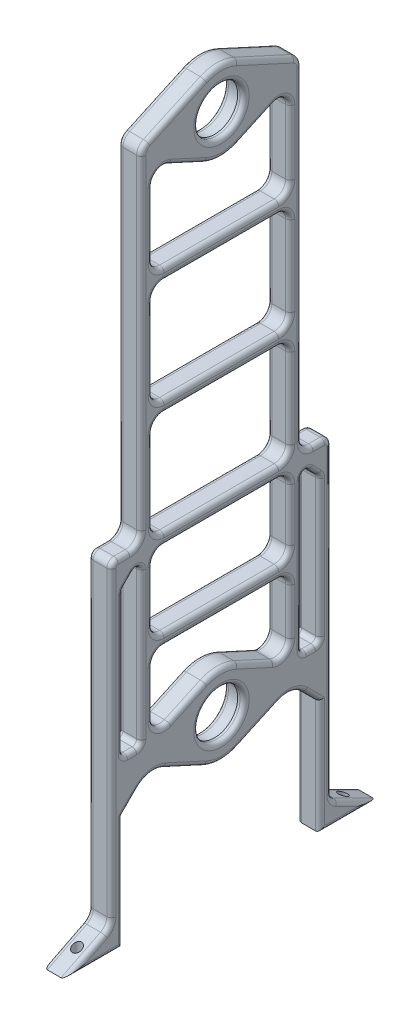
SolidWorks part; units mm, degrees
ref_plane "Front Plane" through (0, 0, 0) normal (0, 0, 1) x (1, 0, 0)
ref_plane "Top Plane" through (0, 0, 0) normal (0, 1, 0) x (1, 0, 0)
ref_plane "Right Plane" through (0, 0, 0) normal (1, 0, 0) x (0, 0, -1)
sketch "Croquis1" plane through (0, 0, 0) normal (1, 0, 0) x (0, 0, -1)
  line L0 (3.1865, 95.253) -> (51.7799, 95.253) construction
  line L1 (15, 74) -> (5, 64)
  line L2 (0, 0) -> (5, 0)
  line L3 (0, 0) -> (0, 155)
  line L4 (0, 155) -> (5, 155)
  line L5 (5, 0) -> (5, 155)
  line L6 (5, 155) -> (91, 155)
  line L7 (5, 155) -> (5, 150)
  line L8 (5, 150) -> (91, 150)
  line L9 (91, 155) -> (91, 150)
  line L10 (91, 155) -> (96, 155)
  line L11 (91, 155) -> (91, 0)
  line L12 (91, 0) -> (96, 0)
  line L13 (96, 155) -> (96, 0)
  line L14 (13, 305) -> (18, 305)
  line L15 (13, 305) -> (13, 79)
  line L16 (13, 79) -> (18, 79)
  line L17 (18, 305) -> (18, 79)
  line L18 (5, 79) -> (91, 79)
  line L19 (5, 79) -> (5, 74)
  line L20 (5, 74) -> (91, 74)
  line L21 (91, 79) -> (91, 74)
  line L22 (83, 79) -> (78, 79)
  line L23 (83, 79) -> (83, 305)
  line L24 (83, 305) -> (78, 305)
  line L25 (78, 79) -> (78, 305)
  line L26 (18, 305) -> (78, 305)
  line L27 (18, 305) -> (18, 300)
  line L28 (18, 300) -> (78, 300)
  line L29 (78, 305) -> (78, 300)
  line L30 (18, 205) -> (78, 205)
  line L31 (18, 205) -> (18, 200)
  line L32 (18, 200) -> (78, 200)
  line L33 (78, 205) -> (78, 200)
  line L34 (18, 255) -> (78, 255)
  line L35 (18, 255) -> (18, 250)
  line L36 (18, 250) -> (78, 250)
  line L37 (78, 255) -> (78, 250)
  line L38 (18, 117) -> (78, 117)
  line L39 (18, 117) -> (18, 112)
  line L40 (18, 112) -> (78, 112)
  line L41 (78, 117) -> (78, 112)
  line L42 (81, 74) -> (91, 64)
  line L43 (78, 52.6217) -> (83, 52.6217) construction
  line L44 (48, 117) -> (48, 112) construction
  line L45 (48, 155) -> (48, 150) construction
  line L46 (48, 200) -> (48, 205) construction
  line L47 (48, 255) -> (48, 250) construction
  line L48 (48, 250) -> (48, 255) construction
  line L49 (48, 305) -> (48, 300) construction
  line L50 (22.0711, 74) -> (5, 56.9289)
  line L51 (73.9289, 74) -> (91, 56.9289)
  line L52 (48, 300) -> (48, 255) construction
  line L53 (48, 250) -> (48, 205) construction
  line L54 (48, 205) -> (48, 334.4288) construction
  line L55 (48, 200) -> (48, 155) construction
  line L56 (48, 150) -> (48, 117) construction
  line L57 (48, 112) -> (48, 79) construction
  line L58 (48, 74) -> (48, 0) construction
  line L59 (13, 150) -> (5, 142)
  line L60 (83, 150) -> (91, 142)
  point P59 (48, 79)
  point P64 (48, 74)
  dimension "D2" = 70
  dimension "D3" = 5
  dimension "D4" = 45
  dimension "D5" = 45
  dimension "D6" = 5
  dimension "D7" = 5
  dimension "D8" = 5
  dimension "D9" = 10
  dimension "D10" = 10
  dimension "D11" = 45
  dimension "D12" = 45
  dimension "D13" = 8
  dimension "D14" = 74
  dimension "D16" = 150
extrude "Saliente-Extruir1" add sketch "Croquis1" along normal blind 10 contours L2 L5 L4 L3 | L50 L20 L1 L5 | L5 L20 L11 L18 L16 | L13 L10 L9 L11 L12 | L20 L51 L11 L42 | L25 L18 L23 L8 | L17 L8 L15 L16 | L17 L40 L25 L38 | L15 L6 L5 L8 | L17 L6 L15 L8 | L8 L25 L6 L17 | L17 L14 L15 L6 | L25 L8 L23 L6 | L25 L6 L23 L24 | L23 L8 L9 L6 | L17 L28 L25 L26 | L17 L36 L25 L34 | L17 L32 L25 L30 | L59 L8 L5 | L8 L60 L11 | L20 L5 L1 | L20 L42 L11 region at (0, 67.0783, -11.9217) region at (0, 70.6667, -8.3333) region at (0, 76.5, -48) region at (0, 77.5, -2.5) region at (0, 67.0783, -84.0783) region at (0, 147.3333, -7.6667) region at (0, 114.5, -15.5) region at (0, 70.6667, -87.6667) region at (0, 77.5, -93.5) region at (0, 152.5, -9) region at (0, 152.5, -15.5) region at (0, 152.5, -48) region at (0, 230, -15.5) region at (0, 114.5, -48) region at (0, 114.5, -80.5) region at (0, 152.5, -80.5) region at (0, 147.3333, -88.3333) region at (0, 152.5, -87) region at (0, 230, -80.5) region at (0, 202.5, -48) region at (0, 302.5, -48) region at (0, 252.5, -48)
sketch "Croquis2" plane through (10, 0, 0) normal (1, 0, 0) x (0, 0, -1)
  line L0 (48, 301.5) -> (34.0198, 331.4807) construction
  line L1 (48, 301.5) -> (81.08, 301.5) construction
  line L2 (48, 73.5) -> (48, 301.5) construction
  line L3 (106.66, 301.5) -> (55.5, 301.5)
  line L4 (22.42, 73.5) -> (22.42, 301.5)
  line L5 (73.58, 301.5) -> (73.58, 136.78) construction
  line L6 (106.66, 301.5) -> (106.66, 272.7)
  line L7 (106.66, 272.7) -> (55.5, 272.7)
  line L8 (55.5, 301.5) -> (55.5, 272.7)
  line L9 (22.42, 301.5) -> (22.42, 73.5) construction
  line L10 (8.4398, 331.4807) -> (59.5998, 331.4807)
  line L11 (8.4398, 331.4807) -> (8.4398, 302.6807)
  line L12 (8.4398, 302.6807) -> (59.5998, 302.6807)
  line L13 (59.5998, 331.4807) -> (59.5998, 302.6807)
  line L18 (73.58, 136.78) -> (73.58, 73.5) construction
  line L19 (48, 73.5) -> (14.92, 73.5) construction
  line L20 (-10.66, 73.5) -> (40.5, 73.5)
  line L21 (-10.66, 73.5) -> (-10.66, 44.7)
  line L22 (-10.66, 44.7) -> (40.5, 44.7)
  line L23 (40.5, 73.5) -> (40.5, 44.7)
  line L24 (36.4002, 43.5193) -> (87.5602, 43.5193)
  line L25 (36.4002, 43.5193) -> (36.4002, 14.7193)
  line L26 (36.4002, 14.7193) -> (87.5602, 14.7193)
  line L27 (87.5602, 43.5193) -> (87.5602, 14.7193)
  line L28 (48, 73.5) -> (61.9802, 43.5193) construction
  line L29 (62.5413, 301.5) -> (55.5, 295.71)
  line L30 (55.5, 295.71) -> (59.5573, 272.7)
  line L32 (52.5584, 331.4807) -> (59.5998, 325.6907)
  line L33 (59.5998, 325.6907) -> (55.5425, 302.6807)
  line L34 (73.58, 73.5) -> (73.58, 301.5)
  line L35 (-10.66, 124.84) -> (40.5, 124.84)
  line L36 (-10.66, 124.84) -> (-10.66, 96.04)
  line L37 (-10.66, 96.04) -> (40.5, 96.04)
  line L38 (40.5, 124.84) -> (40.5, 96.04)
  line L39 (55.5, 96.14) -> (106.66, 96.14)
  line L40 (55.5, 96.14) -> (55.5, 67.34)
  line L41 (55.5, 67.34) -> (106.66, 67.34)
  line L42 (106.66, 96.14) -> (106.66, 67.34)
  line L43 (-10.66, 176.18) -> (40.5, 176.18)
  line L44 (-10.66, 176.18) -> (-10.66, 147.38)
  line L45 (-10.66, 147.38) -> (40.5, 147.38)
  line L46 (40.5, 176.18) -> (40.5, 147.38)
  line L47 (-10.66, 227.52) -> (40.5, 227.52)
  line L48 (-10.66, 227.52) -> (-10.66, 198.72)
  line L49 (-10.66, 198.72) -> (40.5, 198.72)
  line L50 (40.5, 227.52) -> (40.5, 198.72)
  line L51 (-10.66, 278.86) -> (40.5, 278.86)
  line L52 (-10.66, 278.86) -> (-10.66, 250.06)
  line L53 (-10.66, 250.06) -> (40.5, 250.06)
  line L54 (40.5, 278.86) -> (40.5, 250.06)
  line L55 (55.5, 250.16) -> (106.66, 250.16)
  line L56 (55.5, 250.16) -> (55.5, 221.36)
  line L57 (55.5, 221.36) -> (106.66, 221.36)
  line L58 (106.66, 250.16) -> (106.66, 221.36)
  line L59 (55.5, 198.82) -> (106.66, 198.82)
  line L60 (55.5, 198.82) -> (55.5, 170.02)
  line L61 (55.5, 170.02) -> (106.66, 170.02)
  line L62 (106.66, 198.82) -> (106.66, 170.02)
  line L63 (55.5, 147.48) -> (106.66, 147.48)
  line L64 (55.5, 147.48) -> (55.5, 118.68)
  line L65 (55.5, 118.68) -> (106.66, 118.68)
  line L66 (106.66, 147.48) -> (106.66, 118.68)
  line L67 (13, 301.5) -> (83, 301.5) construction
  line L70 (13, 305) -> (13, 155) construction
  line L71 (83, 155) -> (83, 305) construction
  line L73 (18, 300) -> (78, 300) construction
  circle A2 centre (48, 301.5) radius 25.58
  circle A3 centre (48, 73.5) radius 25.58
  arc A4 (22.42, 73.5) -> (73.58, 73.5) centre (48, 73.5) ccw
  arc A5 (73.58, 301.5) -> (22.42, 301.5) centre (48, 301.5) ccw
  point P8 (48, 187.5)
  point P9 (48, 301.5)
  point P11 (81.08, 301.5)
  point P20 (34.0198, 331.4807)
  point P34 (61.9802, 43.5193)
  point P37 (14.92, 73.5)
  point P52 (22.42, 124.84)
  point P53 (73.58, 96.14)
  point P58 (14.92, 124.84)
  point P59 (81.08, 96.14)
  point P80 (22.42, 278.86)
  point P81 (22.42, 227.52)
  point P82 (22.42, 176.18)
  point P83 (73.58, 250.16)
  point P84 (73.58, 198.82)
  point P85 (73.58, 147.48)
  point P86 (14.92, 278.86)
  point P87 (14.92, 227.52)
  point P88 (14.92, 176.18)
  point P93 (81.08, 250.16)
  point P94 (81.08, 198.82)
  point P95 (81.08, 147.48)
  dimension "D1" = 51.16
  dimension "D3" = 51.16
  dimension "D7" = 33.08
  dimension "D30" = 228
  dimension "D4" = 115
  dimension "D5" = 28.8
  dimension "D6" = 115
  dimension "D8" = 140.57
  dimension "D9" = 140.57
  dimension "D10" = 23.01
  dimension "D11" = 23.01
  dimension "D12" = 10
  dimension "D13" = 10
  dimension "D14" = 7.5
  dimension "D15" = 7.5
  dimension "D16" = 51.34
  dimension "D17" = 7.5
  dimension "D18" = 7.5
  dimension "D19" = 7.5
  dimension "D20" = 7.5
  dimension "D21" = 7.5
  dimension "D22" = 7.5
  dimension "D23" = 51.34
  dimension "D24" = 51.34
  dimension "D25" = 51.34
  dimension "D26" = 51.34
  dimension "D27" = 51.34
  dimension "D28" = 51.34
  dimension "D29" = 51.34
  dimension "D31" = 1.5
sketch "Croquis3" plane through (10, 0, 0) normal (1, 0, 0) x (0, 0, -1)
  line L0 (13, 301.5) -> (83, 301.5) construction
  line L1 (106.66, 301.5) -> (55.5, 301.5) construction
  line L2 (13, 305) -> (13, 155) construction
  line L3 (83, 155) -> (83, 305) construction
  line L5 (15.9167, 306.0453) -> (40.7083, 317.4085)
  line L6 (80.0833, 306.0453) -> (55.2917, 317.4085)
  line L7 (15.9167, 296.9547) -> (40.7083, 285.5915)
  line L8 (80.0833, 296.9547) -> (55.2917, 285.5915)
  line L9 (14.4293, 305) -> (13, 305)
  line L10 (13, 305) -> (83, 305) construction
  line L11 (13, 305) -> (13, 301.5)
  line L12 (81.5707, 305) -> (83, 305)
  line L13 (83, 305) -> (83, 301.5)
  circle A0 centre (48, 301.5) radius 10.01
  circle A1 centre (48, 301.5) radius 11.01
  circle A2 centre (48, 301.5) radius 17.5
  circle A3 centre (18, 301.5) radius 5
  circle A4 centre (78, 301.5) radius 5
  line M13 (78, 300) -> (78, 255)
  line M15 (18, 255) -> (18, 300)
  line M16 (18, 300) -> (78, 300)
  line M18 (83, 305) -> (13, 305)
  dimension "D1" = 22.02
  dimension "D2" = 20.02
  dimension "D3" = 35
  dimension "D4" = 10
extrude "Saliente-Extruir2" add sketch "Croquis3" against normal up to surface (10 mm away) contours A2 A1 M18 | A3 A2 L5 M18 | A3 M18 | A3 M18 M15 M16 | A3 M15 M16 | A3 L7 A2 M15 M16 | A2 A1 M16 | A4 A2 L8 M16 M13 | A4 L6 A2 M18 | A3 A2 M16 M18 | A2 A1 M18 M16 | A2 A1 M16 M18 | A4 A2 M18 M16 | A4 M16 M13 | A4 M18 M16 M13 | A4 M18 region at (10, 305.6085, -18) region at (10, 308.8289, -27.6858) region at (10, 318.6296, -48) region at (10, 301.5988, -17.6014) region at (10, 302.574, -26.6181) region at (10, 308.8289, -68.3142) region at (10, 302.5112, -33.8615) region at (10, 305.6085, -78) region at (10, 302.574, -69.3819) region at (10, 302.5112, -62.1385) region at (10, 299.6163, -33.8285) region at (10, 295.0098, -27.5107) region at (10, 298.5471, -19.9168) region at (10, 301.5988, -78.3986) region at (10, 298.5471, -76.0832) region at (10, 295.0098, -68.4893) up to face at (0, 227.5, -48)
sketch "Croquis7" plane through (10, 0, 0) normal (1, 0, 0) x (0, 0, -1)
  line L0 (14.4293, 305) -> (13, 305)
  line L1 (22.0711, 74) -> (73.9289, 74)
  line L7 (81.5707, 305) -> (83, 305)
  line L12 (22.0711, 74) -> (73.9289, 74)
  line L29 (83, 155) -> (83, 305)
  line L30 (83, 155) -> (83, 305)
  line L31 (83, 305) -> (81.5707, 305)
  line L32 (83, 305) -> (81.5707, 305)
  line L33 (80.0833, 306.0453) -> (55.2917, 317.4085)
  line L34 (80.0833, 306.0453) -> (55.2917, 317.4085)
  line L35 (40.7083, 317.4085) -> (15.9167, 306.0453)
  line L36 (40.7083, 317.4085) -> (15.9167, 306.0453)
  line L37 (14.4293, 305) -> (13, 305)
  line L38 (14.4293, 305) -> (13, 305)
  line L39 (13, 305) -> (13, 155)
  line L40 (13, 305) -> (13, 155)
  line L41 (13, 155) -> (0, 155)
  line L42 (13, 155) -> (0, 155)
  line L43 (0, 155) -> (0, 0)
  line L44 (0, 155) -> (0, 0)
  line L45 (0, 0) -> (5, 0)
  line L46 (0, 0) -> (5, 0)
  line L47 (5, 0) -> (5, 56.9289)
  line L48 (5, 0) -> (5, 56.9289)
  line L49 (5, 56.9289) -> (22.0711, 74)
  line L50 (5, 56.9289) -> (22.0711, 74)
  line L51 (73.9289, 74) -> (91, 56.9289)
  line L52 (73.9289, 74) -> (91, 56.9289)
  line L53 (91, 56.9289) -> (91, 0)
  line L54 (91, 56.9289) -> (91, 0)
  line L55 (91, 0) -> (96, 0)
  line L56 (91, 0) -> (96, 0)
  line L57 (96, 0) -> (96, 155)
  line L58 (96, 0) -> (96, 155)
  line L59 (96, 155) -> (83, 155)
  line L60 (96, 155) -> (83, 155)
  circle A0 centre (18, 301.5) radius 5
  arc A1 (15.9167, 306.0453) -> (14.4293, 305) centre (18, 301.5) ccw
  circle A7 centre (78, 301.5) radius 5
  arc A12 (15.9167, 306.0453) -> (14.4293, 305) centre (18, 301.5) ccw
  arc A15 (81.5707, 305) -> (80.0833, 306.0453) centre (78, 301.5) ccw
  arc A16 (81.5707, 305) -> (80.0833, 306.0453) centre (78, 301.5) ccw
  arc A17 (55.2917, 317.4085) -> (40.7083, 317.4085) centre (48, 301.5) ccw
  arc A18 (55.2917, 317.4085) -> (40.7083, 317.4085) centre (48, 301.5) ccw
  dimension "D1" = 0
extrude "Cortar-Extruir5" cut sketch "Croquis7" against normal through all both and the other way through all contours A7 L30 L7 | A0 L0 L40 region at (10, 304.152, -13.4158) region at (10, 304.152, -82.5842)
pattern_linear "MatrizL2" count 2 spacing 228 along (0, -1, 0) of "Saliente-Extruir2"
sketch "Croquis10" plane through (10, 0, 0) normal (1, 0, 0) x (0, 0, -1)
  line L0 (96, 0) -> (96, 155) construction
  line L1 (0, 0) -> (96, 0)
  line L2 (0, 0) -> (0, 7.2193)
  line L3 (0, 7.2193) -> (96, 7.2193)
  line L4 (96, 0) -> (96, 7.2193)
  line L5 (36.4002, 14.7193) -> (87.5602, 14.7193) construction
  dimension "D1" = 7.5
extrude "Cortar-Extruir6" cut sketch "Croquis10" against normal through all both and the other way through all
sketch "Croquis11" plane through (10, 0, 0) normal (1, 0, 0) x (0, 0, -1)
  line L0 (0, 7.2193) -> (-20, 7.2193)
  line L1 (-20, 7.2193) -> (0, 17.2193)
  line L2 (0, 155) -> (0, 0) construction
  line L3 (0, 17.2193) -> (0, 7.2193)
  line L4 (48, 73.5) -> (48, -15.6705) construction
  line L5 (96, 7.2193) -> (116, 7.2193)
  line L6 (96, 17.2193) -> (96, 7.2193)
  line L7 (116, 7.2193) -> (96, 17.2193)
  dimension "D1" = 20
  dimension "D2" = 10
extrude "Saliente-Extruir4" add sketch "Croquis11" against normal up to surface (10 mm away) contours L3 L1 L0 | L5 L7 L6 region at (10, 10.5527, 6.6667) region at (10, 10.5527, -102.6667) up to face at (0, 93.7348, -48)
sketch "Croquis12" plane through (0, 7.2193, 0) normal (0, -1, 0) x (1, 0, 0)
  line L1 (0, -5) -> (0, 20) construction
  circle A0 centre (5, 10) radius 2
  dimension "D1" = 4
  dimension "D2" = 10
  dimension "D3" = 5
extrude "Cortar-Extruir7" cut sketch "Croquis12" against normal through all both and the other way through all
ref_plane "Plano3" through (0, 0, -48) normal (0, 0, 1) x (1, 0, 0)
mirror "Simetría1" about plane through (0, 0, -48) normal (0, 0, 1) of "Cortar-Extruir7"
sketch "Croquis16" plane through (0, 0, 0) normal (-1, 0, 0) x (0, 0, 1)
  circle A0 centre (-48, 301.5) radius 11.01
  circle A1 centre (-48, 73.5) radius 11.01
extrude "Cortar-Extruir8" cut sketch "Croquis16" against normal through all both and the other way through all
sketch "Croquis17" plane through (10, 0, 0) normal (1, 0, 0) x (0, 0, -1)
  circle A0 centre (48, 301.5) radius 11.01
  circle A1 centre (48, 301.5) radius 10.1
  circle A2 centre (48, 73.5) radius 11.01
  circle A3 centre (48, 73.5) radius 10.1
  dimension "D1" = 20.2
  dimension "D2" = 20.2
extrude "Saliente-Extruir5" add sketch "Croquis17" against normal blind 2 contours A0 A1 | A2 A3 region at (10, 301.5, -37.3014) region at (10, 73.5, -37.3014)
sketch "Croquis18" plane through (10, 0, 0) normal (1, 0, 0) x (0, 0, -1)
  line L0 (18, 295.9998) -> (40.7083, 285.5915) construction
  line L1 (18, 295.9998) -> (18, 255) construction
  line L2 (78, 295.9998) -> (55.2917, 285.5915) construction
  line L3 (78, 255) -> (78, 295.9998) construction
  line L4 (18, 112) -> (18, 79.0002) construction
  line L5 (18, 79.0002) -> (40.7083, 89.4085) construction
  line L6 (78, 79.0002) -> (55.2917, 89.4085) construction
  line L7 (78, 79.0002) -> (78, 112) construction
  line L8 (78, 67.9998) -> (55.2917, 57.5915) construction
  line L9 (73.9289, 74) -> (91, 56.9289) construction
  line L10 (5, 56.9289) -> (22.0711, 74) construction
  line L11 (18, 67.9998) -> (40.7083, 57.5915) construction
  line L12 (55.2917, 317.4085) -> (80.0833, 306.0453)
  line L13 (55.2917, 317.4085) -> (80.0833, 306.0453)
  line L14 (83, 301.5) -> (83, 155)
  line L15 (83, 301.5) -> (83, 155)
  line L16 (83, 155) -> (96, 155)
  line L17 (83, 155) -> (96, 155)
  line L18 (96, 155) -> (96, 17.2193)
  line L19 (96, 155) -> (96, 17.2193)
  line L20 (96, 17.2193) -> (116, 7.2193)
  line L21 (96, 17.2193) -> (116, 7.2193)
  line L22 (116, 7.2193) -> (91, 7.2193)
  line L23 (116, 7.2193) -> (91, 7.2193)
  line L24 (91, 7.2193) -> (91, 56.9289)
  line L25 (91, 7.2193) -> (91, 56.9289)
  line L26 (91, 56.9289) -> (79.266, 68.6629)
  line L27 (91, 56.9289) -> (79.266, 68.6629)
  line L28 (78, 68.5) -> (78, 67.9998)
  line L29 (78, 68.5) -> (78, 67.9998)
  line L30 (78, 67.9998) -> (55.2917, 57.5915)
  line L31 (78, 67.9998) -> (55.2917, 57.5915)
  line L32 (91, 7.2193) -> (116, 7.2193)
  line L33 (116, 7.2193) -> (96, 17.2193)
  line L34 (96, 17.2193) -> (96, 155)
  line L35 (96, 155) -> (83, 155)
  line L36 (83, 155) -> (83, 301.5)
  line L37 (80.0833, 306.0453) -> (55.2917, 317.4085)
  line L38 (40.7083, 317.4085) -> (15.9167, 306.0453)
  line L39 (13, 301.5) -> (13, 155)
  line L40 (13, 155) -> (0, 155)
  line L41 (0, 155) -> (0, 17.2193)
  line L42 (0, 17.2193) -> (-20, 7.2193)
  line L43 (-20, 7.2193) -> (5, 7.2193)
  line L44 (5, 7.2193) -> (5, 56.9289)
  line L45 (5, 56.9289) -> (16.734, 68.6629)
  line L46 (18, 68.5) -> (18, 67.9998)
  line L47 (18, 67.9998) -> (40.7083, 57.5915)
  line L48 (55.2917, 57.5915) -> (78, 67.9998)
  line L49 (78, 67.9998) -> (78, 68.5)
  line L50 (79.266, 68.6629) -> (91, 56.9289)
  line L51 (91, 56.9289) -> (91, 7.2193)
  line L52 (91, 7.2193) -> (116, 7.2193)
  line L53 (116, 7.2193) -> (96, 17.2193)
  line L54 (96, 17.2193) -> (96, 155)
  line L55 (96, 155) -> (83, 155)
  line L56 (83, 155) -> (83, 301.5)
  line L57 (80.0833, 306.0453) -> (55.2917, 317.4085)
  line L58 (40.7083, 317.4085) -> (15.9167, 306.0453)
  line L59 (13, 301.5) -> (13, 155)
  line L60 (13, 155) -> (0, 155)
  line L61 (0, 155) -> (0, 17.2193)
  line L62 (0, 17.2193) -> (-20, 7.2193)
  line L63 (-20, 7.2193) -> (5, 7.2193)
  line L64 (5, 7.2193) -> (5, 56.9289)
  line L65 (5, 56.9289) -> (16.734, 68.6629)
  line L66 (18, 68.5) -> (18, 67.9998)
  line L67 (18, 67.9998) -> (40.7083, 57.5915)
  line L68 (55.2917, 57.5915) -> (78, 67.9998)
  line L69 (78, 67.9998) -> (78, 68.5)
  line L70 (79.266, 68.6629) -> (91, 56.9289)
  line L71 (91, 56.9289) -> (91, 7.2193)
  line L72 (40.7083, 57.5915) -> (18, 67.9998)
  line L73 (40.7083, 57.5915) -> (18, 67.9998)
  line L74 (18, 67.9998) -> (18, 68.5)
  line L75 (18, 67.9998) -> (18, 68.5)
  line L76 (16.734, 68.6629) -> (5, 56.9289)
  line L77 (16.734, 68.6629) -> (5, 56.9289)
  line L78 (5, 56.9289) -> (5, 7.2193)
  line L79 (5, 56.9289) -> (5, 7.2193)
  line L80 (5, 7.2193) -> (-20, 7.2193)
  line L81 (5, 7.2193) -> (-20, 7.2193)
  line L82 (-20, 7.2193) -> (0, 17.2193)
  line L83 (-20, 7.2193) -> (0, 17.2193)
  line L84 (0, 17.2193) -> (0, 155)
  line L85 (0, 17.2193) -> (0, 155)
  line L86 (0, 155) -> (13, 155)
  line L87 (0, 155) -> (13, 155)
  line L88 (13, 155) -> (13, 301.5)
  line L89 (13, 155) -> (13, 301.5)
  line L90 (15.9167, 306.0453) -> (40.7083, 317.4085)
  line L91 (15.9167, 306.0453) -> (40.7083, 317.4085)
  line L96 (78, 205) -> (78, 250)
  line L97 (18, 205) -> (78, 205)
  line L98 (18, 250) -> (18, 205)
  line L99 (78, 250) -> (18, 250)
  line L100 (78, 205) -> (78, 250)
  line L101 (18, 205) -> (78, 205)
  line L102 (18, 250) -> (18, 205)
  line L103 (78, 250) -> (18, 250)
  line L104 (78, 155) -> (78, 200)
  line L105 (18, 155) -> (78, 155)
  line L106 (18, 200) -> (18, 155)
  line L107 (78, 200) -> (18, 200)
  line L108 (78, 155) -> (78, 200)
  line L109 (18, 155) -> (78, 155)
  line L110 (18, 200) -> (18, 155)
  line L111 (78, 200) -> (18, 200)
  line L112 (78, 150) -> (18, 150)
  line L113 (78, 117) -> (78, 150)
  line L114 (18, 117) -> (78, 117)
  line L115 (18, 150) -> (18, 117)
  line L116 (78, 150) -> (18, 150)
  line L117 (78, 117) -> (78, 150)
  line L118 (18, 117) -> (78, 117)
  line L119 (18, 150) -> (18, 117)
  line L120 (83, 150) -> (83, 79)
  line L121 (91, 142) -> (83, 150)
  line L122 (91, 79) -> (91, 142)
  line L123 (83, 79) -> (91, 79)
  line L124 (83, 150) -> (83, 79)
  line L125 (91, 142) -> (83, 150)
  line L126 (91, 79) -> (91, 142)
  line L127 (83, 79) -> (91, 79)
  line L128 (13, 150) -> (5, 142)
  line L129 (13, 79) -> (13, 150)
  line L130 (5, 79) -> (13, 79)
  line L131 (5, 142) -> (5, 79)
  line L132 (13, 150) -> (5, 142)
  line L133 (13, 79) -> (13, 150)
  line L134 (5, 79) -> (13, 79)
  line L135 (5, 142) -> (5, 79)
  line L137 (18, 295.9998) -> (18, 255)
  line L138 (40.7083, 285.5915) -> (18, 295.9998)
  line L139 (78, 295.9998) -> (55.2917, 285.5915)
  line L140 (78, 255) -> (78, 295.9998)
  line L141 (18, 255) -> (78, 255)
  line L142 (18, 295.9998) -> (18, 255)
  line L143 (40.7083, 285.5915) -> (18, 295.9998)
  line L144 (78, 295.9998) -> (55.2917, 285.5915)
  line L145 (78, 255) -> (78, 295.9998)
  line L146 (18, 255) -> (78, 255)
  line L147 (78, 79.0002) -> (78, 112)
  line L148 (55.2917, 89.4085) -> (78, 79.0002)
  line L149 (18, 79.0002) -> (40.7083, 89.4085)
  line L150 (18, 112) -> (18, 79.0002)
  line L151 (78, 112) -> (18, 112)
  line L152 (78, 79.0002) -> (78, 112)
  line L153 (55.2917, 89.4085) -> (78, 79.0002)
  line L154 (18, 79.0002) -> (40.7083, 89.4085)
  line L155 (18, 112) -> (18, 79.0002)
  line L156 (78, 112) -> (18, 112)
  circle A0 centre (18.8315, 56.6183) radius 10
  circle A1 centre (77.1685, 56.6183) radius 10
  circle A2 centre (73, 86.7921) radius 5
  circle A3 centre (23, 86.7921) radius 5
  circle A4 centre (23, 288.2079) radius 5
  circle A5 centre (73, 288.2079) radius 5
  arc A6 (83, 301.5) -> (80.0833, 306.0453) centre (78, 301.5) ccw
  arc A7 (83, 301.5) -> (80.0833, 306.0453) centre (78, 301.5) ccw
  arc A8 (78, 68.5) -> (79.266, 68.6629) centre (78, 73.5) ccw
  arc A9 (78, 68.5) -> (79.266, 68.6629) centre (78, 73.5) ccw
  arc A10 (40.7083, 57.5915) -> (55.2917, 57.5915) centre (48, 73.5) ccw
  arc A11 (40.7083, 57.5915) -> (55.2917, 57.5915) centre (48, 73.5) ccw
  arc A12 (83, 301.5) -> (80.0833, 306.0453) centre (78, 301.5) ccw
  arc A13 (55.2917, 317.4085) -> (40.7083, 317.4085) centre (48, 301.5) ccw
  arc A14 (15.9167, 306.0453) -> (13, 301.5) centre (18, 301.5) ccw
  arc A15 (16.734, 68.6629) -> (18, 68.5) centre (18, 73.5) ccw
  arc A16 (40.7083, 57.5915) -> (55.2917, 57.5915) centre (48, 73.5) ccw
  arc A17 (78, 68.5) -> (79.266, 68.6629) centre (78, 73.5) ccw
  arc A18 (83, 301.5) -> (80.0833, 306.0453) centre (78, 301.5) ccw
  arc A19 (55.2917, 317.4085) -> (40.7083, 317.4085) centre (48, 301.5) ccw
  arc A20 (15.9167, 306.0453) -> (13, 301.5) centre (18, 301.5) ccw
  arc A21 (16.734, 68.6629) -> (18, 68.5) centre (18, 73.5) ccw
  arc A22 (40.7083, 57.5915) -> (55.2917, 57.5915) centre (48, 73.5) ccw
  arc A23 (78, 68.5) -> (79.266, 68.6629) centre (78, 73.5) ccw
  arc A24 (16.734, 68.6629) -> (18, 68.5) centre (18, 73.5) ccw
  arc A25 (16.734, 68.6629) -> (18, 68.5) centre (18, 73.5) ccw
  arc A26 (15.9167, 306.0453) -> (13, 301.5) centre (18, 301.5) ccw
  arc A27 (15.9167, 306.0453) -> (13, 301.5) centre (18, 301.5) ccw
  arc A28 (55.2917, 317.4085) -> (40.7083, 317.4085) centre (48, 301.5) ccw
  arc A29 (55.2917, 317.4085) -> (40.7083, 317.4085) centre (48, 301.5) ccw
  arc A31 (40.7083, 285.5915) -> (55.2917, 285.5915) centre (48, 301.5) ccw
  arc A32 (40.7083, 285.5915) -> (55.2917, 285.5915) centre (48, 301.5) ccw
  arc A33 (55.2917, 89.4085) -> (40.7083, 89.4085) centre (48, 73.5) ccw
  arc A34 (55.2917, 89.4085) -> (40.7083, 89.4085) centre (48, 73.5) ccw
  circle A35 centre (48, 301.5) radius 10.1
  circle A36 centre (48, 301.5) radius 10.1
  circle A37 centre (48, 73.5) radius 10.1
  circle A38 centre (48, 73.5) radius 10.1
  dimension "D1" = 20
  dimension "D2" = 10
  dimension "D3" = 10
  dimension "D4" = 0
  dimension "D5" = 0
  dimension "D6" = 0
  dimension "D7" = 0
  dimension "D8" = 0
  dimension "D9" = 0
  dimension "D10" = 0
  dimension "D11" = 0
  dimension "D12" = 0
  dimension "D13" = 0
extrude "Saliente-Extruir6" add sketch "Croquis18" against normal up to surface (10 mm away) contours A3 L155 L154 | A21 L77 A0 L67 L66 | A9 L29 L31 A1 L70 | A2 L153 L152 | A5 L145 L144 | A4 L143 L142 region at (10, 66.9915, -79.0027) region at (10, 66.9915, -16.9973) region at (10, 293.345, -19.7035) region at (10, 293.345, -76.2965) region at (10, 81.655, -76.2965) region at (10, 81.655, -19.7035) up to face at (0, 93.7348, -48)
fillet "Redondeo1" radius 5 16 edges at (5, 250, -78) (5, 200, -78) (5, 150, -78) (5, 112, -78) (5, 112, -18) (5, 150, -18) (5, 200, -18) (5, 250, -18) (5, 117, -18) (5, 117, -78) (5, 155, -78) (5, 155, -18) (5, 205, -18) (5, 255, -78) (5, 205, -78) (5, 255, -18)
fillet "Redondeo2" radius 5 2 edges at (5, 17.2193, -96) (5, 17.2193, 0)
fillet "Redondeo3" radius 2 4 edges at (5, 79, -83) (5, 79, -91) (5, 79, -13) (5, 79, -5)
fillet "Redondeo4" radius 3 2 edges at (5, 142, -91) (5, 142, -5)
fillet "Redondeo5" radius 2 2 edges at (5, 150, -83) (5, 150, -13)
fillet "Redondeo6" radius 5 2 edges at (5, 155, -83) (5, 155, -13)
fillet "Redondeo7" radius 3 2 edges at (5, 155, -96) (5, 155, 0)
fillet "Redondeo8" radius 2 90 edges at (0, 301.5, -59.01) (0, 79.5858, -12.4142) (0, 79, -9) (0, 79.5858, -5.5858) (0, 110.8787, -5) (0, 141.9054, -5.2284) (0, 144.7322, -7.7322) (0, 147.0193, -11.7654) (0, 113.0858, -13) (0, 147.0193, -84.2346) (0, 144.7322, -88.2678) (0, 141.9054, -90.7716) (0, 110.8787, -91) (0, 79.5858, -90.4142) (0, 79, -87) (0, 79.5858, -83.5858) (0, 113.0858, -83) (0, 148.5355, -76.5355) (0, 133.5, -78) (0, 118.4645, -76.5355) (0, 117, -48) (0, 118.4645, -19.4645) (0, 133.5, -18) (0, 148.5355, -19.4645) (0, 150, -48) (0, 156.4645, -19.4645) (0, 177.5, -18) (0, 198.5355, -19.4645) (0, 200, -48) (0, 198.5355, -76.5355) (0, 274.1039, -78) (0, 156.4645, -76.5355) (0, 155, -48) (0, 206.4645, -19.4645) (0, 227.5, -18) (0, 248.5355, -19.4645) (0, 250, -48) (0, 248.5355, -76.5355) (0, 96.8961, -78) (0, 206.4645, -76.5355) (0, 205, -48) (0, 73.5, -59.01) (0, 156.4645, -84.4645) (0, 230.75, -83) (0, 304.2003, -82.2081) (0, 311.7269, -67.6875) (0, 319, -48) (0, 311.7269, -28.3125) (0, 304.2003, -13.7919) (0, 230.75, -13) (0, 156.4645, -11.5355) (0, 155, -5.5) (0, 154.1213, -0.8787) (0, 86.1548, 0) (0, 17.6809, 0.7467) (0, 11.5284, 11.382) (0, 7.2193, 7.5) (0, 32.0741, -5) (0, 60.3092, -8.3802) (0, 66.4606, -17.0628) (0, 61.6502, -31.8533) (0, 56, -48) (0, 61.6502, -64.1467) (0, 66.4606, -78.9372) (0, 60.3092, -87.6198) (0, 32.0741, -91) (0, 7.2193, -103.5) (0, 11.5284, -107.382) (0, 17.6809, -96.7467) (0, 86.1548, -96) (0, 154.1213, -95.1213) (0, 155, -90.5) (0, 85.8277, -63.1042) (0, 91, -48) (0, 85.8277, -32.8958) (0, 82.584, -20.2997) (0, 96.8961, -18) (0, 110.5355, -19.4645) (0, 112, -48) (0, 110.5355, -76.5355) (0, 82.584, -75.7003) (0, 289.1723, -32.8958) (0, 284, -48) (0, 289.1723, -63.1042) (0, 292.416, -75.7003) (0, 256.4645, -76.5355) (0, 255, -48) (0, 256.4645, -19.4645) (0, 274.1039, -18) (0, 292.416, -20.2997)
fillet "Redondeo9" radius 2 90 edges at (10, 73.5, -58.1) (10, 301.5, -58.1) (10, 141.9054, -5.2284) (10, 110.8787, -5) (10, 79.5858, -5.5858) (10, 79, -9) (10, 79.5858, -12.4142) (10, 113.0858, -13) (10, 147.0193, -11.7654) (10, 144.7322, -7.7322) (10, 79.5858, -90.4142) (10, 110.8787, -91) (10, 141.9054, -90.7716) (10, 144.7322, -88.2678) (10, 147.0193, -84.2346) (10, 113.0858, -83) (10, 79.5858, -83.5858) (10, 79, -87) (10, 118.4645, -19.4645) (10, 117, -48) (10, 118.4645, -76.5355) (10, 133.5, -78) (10, 148.5355, -76.5355) (10, 150, -48) (10, 148.5355, -19.4645) (10, 133.5, -18) (10, 198.5355, -76.5355) (10, 200, -48) (10, 198.5355, -19.4645) (10, 177.5, -18) (10, 156.4645, -19.4645) (10, 155, -48) (10, 156.4645, -76.5355) (10, 274.1039, -78) (10, 248.5355, -76.5355) (10, 250, -48) (10, 248.5355, -19.4645) (10, 227.5, -18) (10, 206.4645, -19.4645) (10, 205, -48) (10, 206.4645, -76.5355) (10, 96.8961, -78) (10, 17.6809, -96.7467) (10, 11.5284, -107.382) (10, 7.2193, -103.5) (10, 32.0741, -91) (10, 60.3092, -87.6198) (10, 66.4606, -78.9372) (10, 61.6502, -64.1467) (10, 56, -48) (10, 61.6502, -31.8533) (10, 66.4606, -17.0628) (10, 60.3092, -8.3802) (10, 32.0741, -5) (10, 7.2193, 7.5) (10, 11.5284, 11.382) (10, 17.6809, 0.7467) (10, 86.1548, 0) (10, 154.1213, -0.8787) (10, 155, -5.5) (10, 156.4645, -11.5355) (10, 230.75, -13) (10, 304.2003, -13.7919) (10, 311.7269, -28.3125) (10, 319, -48) (10, 311.7269, -67.6875) (10, 304.2003, -82.2081) (10, 230.75, -83) (10, 156.4645, -84.4645) (10, 155, -90.5) (10, 154.1213, -95.1213) (10, 86.1548, -96) (10, 110.5355, -76.5355) (10, 112, -48) (10, 110.5355, -19.4645) (10, 96.8961, -18) (10, 82.584, -20.2997) (10, 85.8277, -32.8958) (10, 91, -48) (10, 85.8277, -63.1042) (10, 82.584, -75.7003) (10, 256.4645, -19.4645) (10, 255, -48) (10, 256.4645, -76.5355) (10, 292.416, -75.7003) (10, 289.1723, -63.1042) (10, 284, -48) (10, 289.1723, -32.8958) (10, 292.416, -20.2997) (10, 274.1039, -18)
sketch "Croquis20" plane through (8, 0, 0) normal (-1, 0, 0) x (0, 0, 1)
  circle A1 centre (-48, 73.5) radius 11.01
  circle A2 centre (-48, 73.5) radius 11.01
  circle A3 centre (-48, 301.5) radius 11.01
  circle A4 centre (-48, 301.5) radius 11.01
  circle A5 centre (-48, 301.5) radius 10.1
  circle A6 centre (-48, 301.5) radius 10.1
  circle A7 centre (-48, 73.5) radius 10.1
  circle A8 centre (-48, 73.5) radius 10.1
  dimension "D1" = 0
  dimension "D2" = 0
  dimension "D3" = 0
  dimension "D4" = 0
extrude "Saliente-Extruir7" add sketch "Croquis20" along normal blind 1
